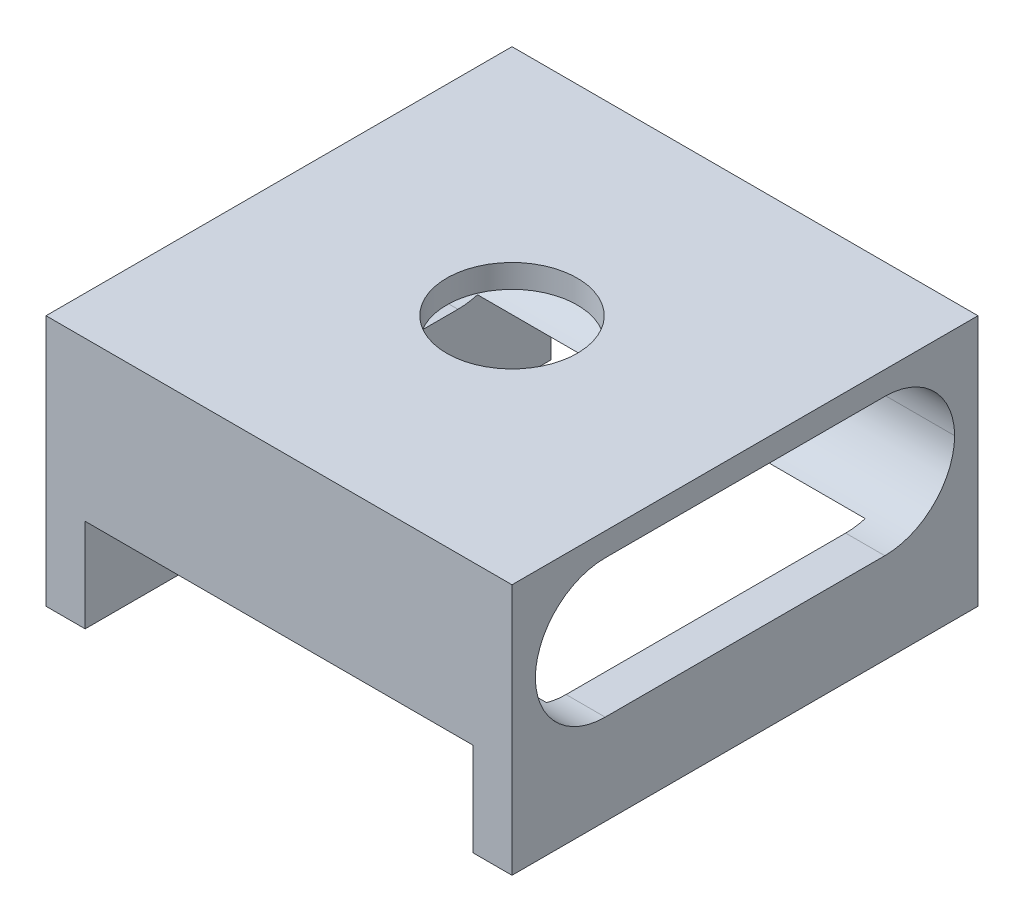
SolidWorks part; units mm, degrees
ref_plane "Front Plane" through (0, 0, 0) normal (0, 0, 1) x (1, 0, 0)
ref_plane "Top Plane" through (0, 0, 0) normal (0, 1, 0) x (1, 0, 0)
ref_plane "Right Plane" through (0, 0, 0) normal (1, 0, 0) x (0, 0, -1)
sketch "Sketch1" plane through (0, 0, 0) normal (0, 1, 0) x (1, 0, 0)
  line L1 (0, 0) -> (31.75, 0)
  line L2 (0, 0) -> (0, 31.75)
  line L3 (0, 31.75) -> (31.75, 31.75)
  line L4 (31.75, 0) -> (31.75, 31.75)
  dimension "D1" = 31.75
  dimension "D2" = 31.75
extrude "Boss-Extrude1" add sketch "Sketch1" along normal blind 17.145
sketch "Sketch2" plane through (0, 17.145, 0) normal (0, 1, 0) x (1, 0, 0)
  line L0 (31.75, 31.75) -> (0, 0) construction
  line L1 (31.75, 0) -> (0, 31.75) construction
  circle A0 centre (15.875, 15.875) radius 4.445
  dimension "D1" = 8.89
extrude "Cut-Extrude1" cut sketch "Sketch2" against normal through all
sketch "Sketch3" plane through (0, 0, 0) normal (0, 0, 1) x (1, 0, 0)
  line L0 (0, 0) -> (31.75, 0) construction
  line L1 (2.667, 0) -> (29.083, 0)
  line L2 (2.667, 0) -> (2.667, 6.35)
  line L3 (2.667, 6.35) -> (29.083, 6.35)
  line L4 (29.083, 0) -> (29.083, 6.35)
  line L5 (15.875, 17.145) -> (15.875, 0) construction
  line L6 (0, 17.145) -> (31.75, 17.145) construction
  point P10 (15.875, 6.35)
  dimension "D1" = 6.35
  dimension "D2" = 26.416
extrude "Cut-Extrude2" cut sketch "Sketch3" against normal through all
sketch "Sketch4" plane through (0, 0, 0) normal (-1, 0, 0) x (0, 0, 1)
  line L0 (-15.875, 17.145) -> (-15.875, 0) construction
  line L1 (-30.1625, 15.5575) -> (-1.5875, 15.5575)
  line L2 (-30.1625, 15.5575) -> (-30.1625, 6.1595)
  line L3 (-30.1625, 6.1595) -> (-1.5875, 6.1595)
  line L4 (-1.5875, 15.5575) -> (-1.5875, 6.1595)
  line L5 (-31.75, 17.145) -> (0, 17.145) construction
  line L6 (-31.75, 0) -> (0, 0) construction
  point P10 (-15.875, 15.5575)
  dimension "D1" = 28.575
  dimension "D2" = 9.398
  dimension "D3" = 1.5875
extrude "Cut-Extrude3" cut sketch "Sketch4" against normal through all
fillet "Fillet2" radius 4.7625 4 edges at (30.4165, 6.1595, -30.1625) (1.3335, 6.1595, -1.5875) (15.875, 15.5575, -1.5875) (15.875, 15.5575, -30.1625)
